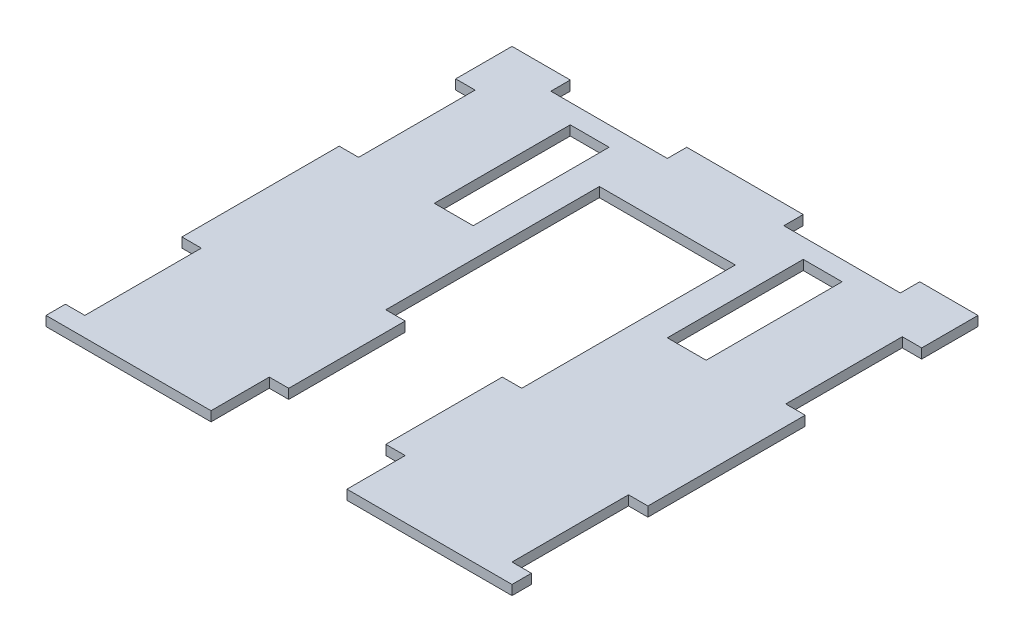
SolidWorks part; units mm, degrees
ref_plane "Front Plane" through (0, 0, 0) normal (0, 0, 1) x (1, 0, 0)
ref_plane "Top Plane" through (0, 0, 0) normal (0, 1, 0) x (1, 0, 0)
ref_plane "Right Plane" through (0, 0, 0) normal (1, 0, 0) x (0, 0, -1)
sketch "Sketch1" plane through (0, 0, 0) normal (0, 1, 0) x (1, 0, 0)
  line L0 (0, -55) -> (0, 55) construction
  line L1 (-152.4, -25.4) -> (152.4, -25.4)
  line L2 (-152.4, -25.4) -> (-152.4, 25.4)
  line L3 (-152.4, 25.4) -> (152.4, 25.4)
  line L4 (152.4, -25.4) -> (152.4, 25.4)
  line L5 (-152.4, -25.4) -> (152.4, 25.4) construction
  line L6 (-152.4, 25.4) -> (152.4, -25.4) construction
  line L7 (-152.4, -25.4) -> (-31.75, -25.4)
  line L8 (-152.4, -25.4) -> (-152.4, -279.4)
  line L9 (-152.4, -279.4) -> (-31.75, -279.4)
  line L10 (-31.75, -25.4) -> (-31.75, -279.4)
  line L11 (31.75, -25.4) -> (31.75, -279.4)
  line L12 (152.4, -279.4) -> (31.75, -279.4)
  line L13 (152.4, -25.4) -> (152.4, -279.4)
  line L14 (152.4, -25.4) -> (31.75, -25.4)
  line L15 (-44.45, -25.4) -> (-44.45, -279.4)
  line L16 (44.45, -25.4) -> (44.45, -279.4)
  point P0 (0, 0)
  dimension "D1" = 304.8
  dimension "D2" = 50.8
  dimension "D3" = 304.8
  dimension "D4" = 120.65
  dimension "D5" = 12.7
extrude "Boss-Extrude1" add sketch "Sketch1" along normal blind 6.35 contours L15 L1 L8 L9 | L14 L16 L12 L13 | L1 L7 L14 L4 L3 L2 region at (0, 0, 0) region at (-98.425, 0, 152.4) region at (98.425, 0, 152.4)
sketch "Sketch2" plane through (0, 6.35, 0) normal (0, 1, 0) x (1, 0, 0)
  line L0 (152.4, -279.4) -> (152.4, 25.4) construction
  line L1 (152.4, -11.43) -> (139.7, -11.43)
  line L2 (152.4, -11.43) -> (152.4, -87.63)
  line L3 (152.4, -87.63) -> (139.7, -87.63)
  line L4 (139.7, -11.43) -> (139.7, -87.63)
  line L5 (-152.4, 25.4) -> (152.4, 25.4) construction
  line L6 (152.4, -190.5) -> (139.7, -190.5)
  line L7 (152.4, -190.5) -> (152.4, -266.7)
  line L8 (152.4, -266.7) -> (139.7, -266.7)
  line L9 (139.7, -190.5) -> (139.7, -266.7)
  line L10 (0, -3.4925) -> (0, 3.4925) construction
  line L11 (-152.4, -266.7) -> (-139.7, -266.7)
  line L12 (-139.7, -190.5) -> (-139.7, -266.7)
  line L13 (-152.4, -190.5) -> (-139.7, -190.5)
  line L14 (-152.4, -190.5) -> (-152.4, -266.7)
  line L15 (-152.4, -87.63) -> (-139.7, -87.63)
  line L16 (-139.7, -11.43) -> (-139.7, -87.63)
  line L17 (-152.4, -11.43) -> (-139.7, -11.43)
  line L18 (-152.4, -11.43) -> (-152.4, -87.63)
  line L19 (-114.3, 12.7) -> (-38.1, 12.7)
  line L20 (114.3, 25.4) -> (38.1, 25.4)
  line L21 (114.3, 25.4) -> (114.3, 12.7)
  line L22 (114.3, 12.7) -> (38.1, 12.7)
  line L23 (38.1, 25.4) -> (38.1, 12.7)
  line L24 (-38.1, 25.4) -> (-38.1, 12.7)
  line L25 (-114.3, 25.4) -> (-38.1, 25.4)
  line L26 (-114.3, 25.4) -> (-114.3, 12.7)
  line L27 (-88.9, -88.9) -> (-63.5, -88.9)
  line L28 (88.9, 0) -> (63.5, 0)
  line L29 (88.9, 0) -> (88.9, -88.9)
  line L30 (88.9, -88.9) -> (63.5, -88.9)
  line L31 (63.5, 0) -> (63.5, -88.9)
  line L32 (-63.5, 0) -> (-63.5, -88.9)
  line L33 (-88.9, 0) -> (-63.5, 0)
  line L34 (-88.9, 0) -> (-88.9, -88.9)
  dimension "D1" = 12.7
  dimension "D2" = 12.7
  dimension "D3" = 76.2
  dimension "D4" = 76.2
  dimension "D5" = 36.83
  dimension "D6" = 215.9
  dimension "D7" = 76.2
  dimension "D8" = 12.7
  dimension "D9" = 76.2
  dimension "D10" = 25.4
  dimension "D11" = 114.3
  dimension "D12" = 63.5
  dimension "D13" = 88.9
extrude "Cut-Extrude1" cut sketch "Sketch2" against normal through all
sketch "Sketch3" plane through (0, 6.35, 0) normal (0, 1, 0) x (1, 0, 0)
  line L0 (44.45, -25.4) -> (44.45, -279.4) construction
  line L1 (44.45, -241.3) -> (31.75, -241.3)
  line L2 (44.45, -241.3) -> (44.45, -165.1)
  line L3 (44.45, -165.1) -> (31.75, -165.1)
  line L4 (31.75, -241.3) -> (31.75, -165.1)
  line L5 (152.4, -279.4) -> (44.45, -279.4) construction
  line L6 (0, -3.4925) -> (0, 3.4925) construction
  line L7 (-44.45, -165.1) -> (-31.75, -165.1)
  line L8 (-31.75, -241.3) -> (-31.75, -165.1)
  line L9 (-44.45, -241.3) -> (-31.75, -241.3)
  line L10 (-44.45, -241.3) -> (-44.45, -165.1)
  dimension "D1" = 12.7
  dimension "D2" = 76.2
  dimension "D3" = 38.1
extrude "Boss-Extrude2" add sketch "Sketch3" against normal blind 6.35
